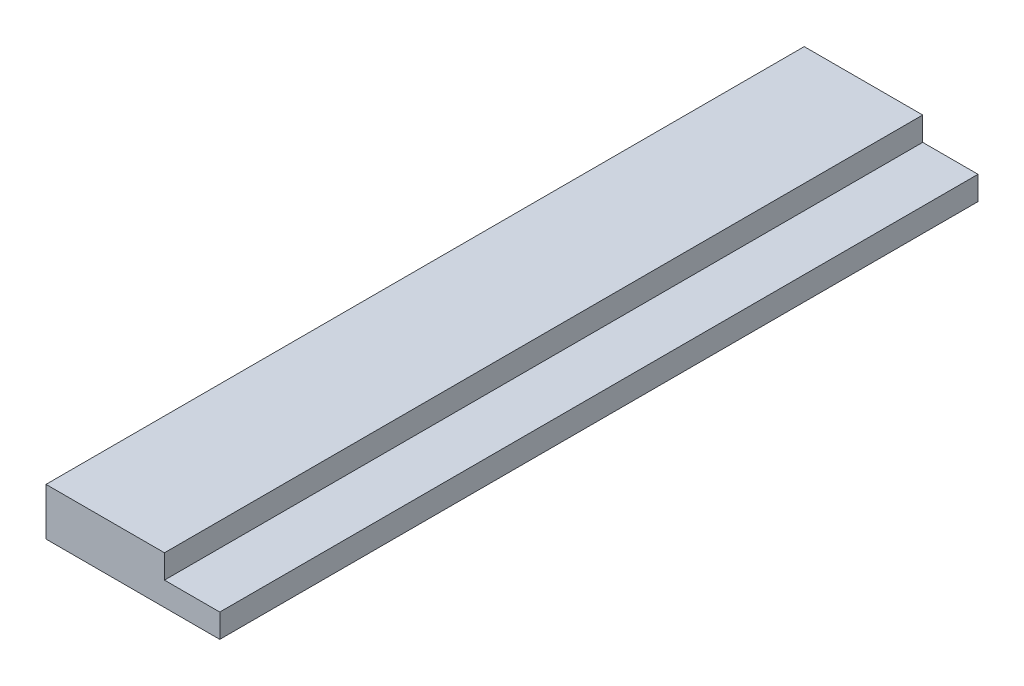
SolidWorks part; units mm, degrees
material "Cedar"
ref_plane "Front Plane" through (0, 0, 0) normal (0, 0, 1) x (1, 0, 0)
ref_plane "Top Plane" through (0, 0, 0) normal (0, 1, 0) x (1, 0, 0)
ref_plane "Right Plane" through (0, 0, 0) normal (1, 0, 0) x (0, 0, -1)
sketch "Sketch1" plane through (0, 0, 0) normal (0, 0, 1) x (1, 0, 0)
  line L1 (-69.85, -19.05) -> (69.85, -19.05)
  line L2 (-69.85, -19.05) -> (-69.85, 19.05)
  line L3 (-69.85, 19.05) -> (69.85, 19.05)
  line L4 (69.85, -19.05) -> (69.85, 19.05)
  line L5 (-69.85, -19.05) -> (69.85, 19.05) construction
  line L6 (-69.85, 19.05) -> (69.85, -19.05) construction
  point P0 (0, 0)
  dimension "D1" = 139.7
  dimension "D2" = 38.1
extrude "Boss-Extrude1" add sketch "Sketch1" along normal blind 304.8 and the other way blind 304.8
sketch "Sketch2" plane through (0, 0, 304.8) normal (0, 0, 1) x (1, 0, 0)
  line L1 (69.85, 19.05) -> (25.4, 19.05)
  line L2 (69.85, 19.05) -> (69.85, 0)
  line L3 (69.85, 0) -> (25.4, 0)
  line L4 (25.4, 19.05) -> (25.4, 0)
  dimension "D1" = 44.45
  dimension "D2" = 19.05
extrude "Cut-Extrude1" cut sketch "Sketch2" against normal through all
